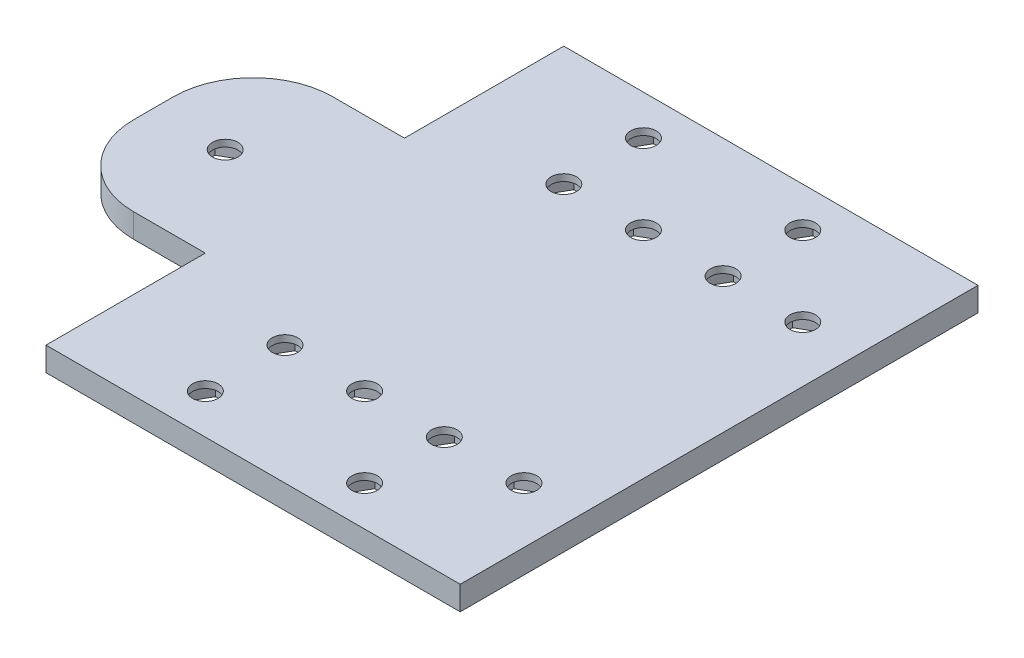
SolidWorks part; units mm, degrees
ref_plane "Front Plane" through (0, 0, 0) normal (0, 0, 1) x (1, 0, 0)
ref_plane "Top Plane" through (0, 0, 0) normal (0, 1, 0) x (1, 0, 0)
ref_plane "Right Plane" through (0, 0, 0) normal (1, 0, 0) x (0, 0, -1)
sketch "Sketch1" plane through (0, 0, 0) normal (0, 1, 0) x (1, 0, 0)
  line L1 (-52, 0) -> (0, 0)
  line L2 (-52, 0) -> (-52, -65)
  line L3 (-52, -65) -> (0, -65)
  line L4 (0, 0) -> (0, -65)
  line L5 (-71, -20) -> (-52, -20)
  line L6 (-71, -20) -> (-71, -45)
  line L7 (-71, -45) -> (-52, -45)
  line L8 (-52, -20) -> (-52, -45)
  dimension "D1" = 52
  dimension "D2" = 65
  dimension "D3" = 20
  dimension "D4" = 20
  dimension "D5" = 19
extrude "Boss-Extrude1" add sketch "Sketch1" along normal blind 3 contours L4 L1 L2 L3 | L6 L7 L2 L5 region at (-26, 0, 32.5) region at (-61.5, 0, 32.5)
sketch "Sketch2" plane through (0, 0, 0) normal (0, -1, 0) x (1, 0, 0)
  line L0 (-46.1813, 60) -> (5.8187, 60) construction
  line L1 (-71, 45) -> (-52, 45) construction
  line L2 (-52, 45) -> (-52, 65) construction
  line L3 (-57.6262, 50) -> (-5.6262, 50) construction
  line L4 (-45.5367, 15) -> (6.4633, 15) construction
  line L5 (-3.975, 48.2535) -> (-3.975, 51.7465)
  line L6 (-3.975, 51.7465) -> (-7, 53.493)
  line L7 (-46.5327, 5) -> (5.4673, 5) construction
  line L8 (-52, 45) -> (-52, 65) construction
  line L9 (0, 0) -> (0, 65) construction
  line L10 (-52, 0) -> (-52, 20) construction
  line L11 (-52, 0) -> (0, 0) construction
  line L12 (-52, 65) -> (0, 65) construction
  line L13 (-27, 80.4391) -> (-27, 0.4391) construction
  line L14 (-33.507, 60) -> (-35.2535, 63.025)
  line L15 (-35.2535, 63.025) -> (-38.7465, 63.025)
  line L16 (-38.7465, 63.025) -> (-40.493, 60)
  line L17 (-40.493, 60) -> (-38.7465, 56.975)
  line L18 (-38.7465, 56.975) -> (-35.2535, 56.975)
  line L19 (-35.2535, 56.975) -> (-33.507, 60)
  line L20 (-18.7465, 56.975) -> (-15.2535, 56.975)
  line L21 (-15.2535, 56.975) -> (-13.507, 60)
  line L22 (-13.507, 60) -> (-15.2535, 63.025)
  line L23 (-15.2535, 63.025) -> (-18.7465, 63.025)
  line L24 (-18.7465, 63.025) -> (-20.493, 60)
  line L25 (-20.493, 60) -> (-18.7465, 56.975)
  line L26 (-15.2535, 46.975) -> (-13.507, 50)
  line L27 (-13.507, 50) -> (-15.2535, 53.025)
  line L28 (-15.2535, 53.025) -> (-18.7465, 53.025)
  line L29 (-18.7465, 53.025) -> (-20.493, 50)
  line L30 (-20.493, 50) -> (-18.7465, 46.975)
  line L31 (-18.7465, 46.975) -> (-15.2535, 46.975)
  line L32 (-35.2535, 46.975) -> (-33.507, 50)
  line L33 (-33.507, 50) -> (-35.2535, 53.025)
  line L34 (-35.2535, 53.025) -> (-38.7465, 53.025)
  line L35 (-38.7465, 53.025) -> (-40.493, 50)
  line L36 (-40.493, 50) -> (-38.7465, 46.975)
  line L37 (-38.7465, 46.975) -> (-35.2535, 46.975)
  line L38 (-35.2535, 11.975) -> (-33.507, 15)
  line L39 (-33.507, 15) -> (-35.2535, 18.025)
  line L40 (-35.2535, 18.025) -> (-38.7465, 18.025)
  line L41 (-38.7465, 18.025) -> (-40.493, 15)
  line L42 (-40.493, 15) -> (-38.7465, 11.975)
  line L43 (-38.7465, 11.975) -> (-35.2535, 11.975)
  line L44 (-15.2535, 11.975) -> (-13.507, 15)
  line L45 (-13.507, 15) -> (-15.2535, 18.025)
  line L46 (-15.2535, 18.025) -> (-18.7465, 18.025)
  line L47 (-18.7465, 18.025) -> (-20.493, 15)
  line L48 (-20.493, 15) -> (-18.7465, 11.975)
  line L49 (-18.7465, 11.975) -> (-15.2535, 11.975)
  line L50 (-13.507, 5) -> (-15.2535, 8.025)
  line L51 (-15.2535, 8.025) -> (-18.7465, 8.025)
  line L52 (-18.7465, 8.025) -> (-20.493, 5)
  line L53 (-20.493, 5) -> (-18.7465, 1.975)
  line L54 (-18.7465, 1.975) -> (-15.2535, 1.975)
  line L55 (-15.2535, 1.975) -> (-13.507, 5)
  line L56 (-38.7465, 8.025) -> (-40.493, 5)
  line L57 (-40.493, 5) -> (-38.7465, 1.975)
  line L58 (-38.7465, 1.975) -> (-35.2535, 1.975)
  line L59 (-35.2535, 1.975) -> (-33.507, 5)
  line L60 (-33.507, 5) -> (-35.2535, 8.025)
  line L61 (-35.2535, 8.025) -> (-38.7465, 8.025)
  line L62 (-62, 62.3352) -> (-62, 22.3352) construction
  line L63 (-23.975, 48.2535) -> (-23.975, 51.7465)
  line L64 (-23.975, 51.7465) -> (-27, 53.493)
  line L65 (-27, 53.493) -> (-30.025, 51.7465)
  line L66 (-30.025, 51.7465) -> (-30.025, 48.2535)
  line L67 (-30.025, 48.2535) -> (-27, 46.507)
  line L68 (-27, 46.507) -> (-23.975, 48.2535)
  line L69 (-23.975, 16.7465) -> (-27, 18.493)
  line L70 (-27, 18.493) -> (-30.025, 16.7465)
  line L71 (-30.025, 16.7465) -> (-30.025, 13.2535)
  line L72 (-30.025, 13.2535) -> (-27, 11.507)
  line L73 (-27, 11.507) -> (-23.975, 13.2535)
  line L74 (-23.975, 13.2535) -> (-23.975, 16.7465)
  line L75 (-7, 53.493) -> (-10.025, 51.7465)
  line L76 (-10.025, 51.7465) -> (-10.025, 48.2535)
  line L77 (-71, 20) -> (-71, 45) construction
  line L84 (-58.975, 34.2465) -> (-62, 35.993)
  line L85 (-62, 35.993) -> (-65.025, 34.2465)
  line L86 (-65.025, 34.2465) -> (-65.025, 30.7535)
  line L87 (-65.025, 30.7535) -> (-62, 29.007)
  line L88 (-62, 29.007) -> (-58.975, 30.7535)
  line L89 (-58.975, 30.7535) -> (-58.975, 34.2465)
  line L90 (-10.025, 48.2535) -> (-7, 46.507)
  line L91 (-7, 46.507) -> (-3.975, 48.2535)
  line L92 (-7, 18.493) -> (-10.025, 16.7465)
  line L93 (-10.025, 16.7465) -> (-10.025, 13.2535)
  line L94 (-10.025, 13.2535) -> (-7, 11.507)
  line L95 (-7, 11.507) -> (-3.975, 13.2535)
  line L96 (-3.975, 13.2535) -> (-3.975, 16.7465)
  line L97 (-3.975, 16.7465) -> (-7, 18.493)
  line L98 (-52, 0) -> (-52, 20) construction
  circle A0 centre (-37, 60) radius 3.025 construction
  circle A1 centre (-17, 60) radius 3.025 construction
  circle A2 centre (-17, 50) radius 3.025 construction
  circle A3 centre (-37, 50) radius 3.025 construction
  circle A4 centre (-37, 15) radius 3.025 construction
  circle A5 centre (-17, 15) radius 3.025 construction
  circle A6 centre (-17, 5) radius 3.025 construction
  circle A7 centre (-37, 5) radius 3.025 construction
  circle A8 centre (-27, 50) radius 3.025 construction
  circle A9 centre (-27, 15) radius 3.025 construction
  circle A10 centre (-7, 50) radius 3.025 construction
  circle A11 centre (-62, 32.5) radius 3.025 construction
  circle A12 centre (-7, 15) radius 3.025 construction
  point P3 (-37, 60)
  point P4 (-17, 50)
  point P5 (-17, 60)
  point P7 (-37, 50)
  point P9 (-37, 5)
  point P13 (-17, 15)
  point P16 (-17, 5)
  point P24 (-37, 15)
  point P91 (-27, 50)
  point P93 (-27, 15)
  point P112 (-62, 32.5)
  point P118 (-7, 50)
  point P120 (-7, 15)
  point P148 (-47, 15)
  point P149 (-6.6463, 15)
  point P150 (-7.2745, 50)
  dimension "D13" = 6.05
  dimension "D14" = 6.05
  dimension "D15" = 6.05
  dimension "D16" = 6.05
  dimension "D17" = 6.05
  dimension "D18" = 6.05
  dimension "D19" = 6.05
  dimension "D20" = 6.05
  dimension "D21" = 6.05
  dimension "D22" = 6.05
  dimension "D26" = 6.05
  dimension "D27" = 12.5
  dimension "D28" = 6.05
  dimension "D29" = 6.05
  dimension "D1" = 15
  dimension "D2" = 17
  dimension "D3" = 17
  dimension "D4" = 15
  dimension "D5" = 15
  dimension "D6" = 17
  dimension "D7" = 15
  dimension "D8" = 17
  dimension "D9" = 5
  dimension "D10" = 15
  dimension "D11" = 5
  dimension "D12" = 15
  dimension "D23" = 15
  dimension "D24" = 15
  dimension "D25" = 27
  dimension "D30" = 9
  dimension "D31" = 10
  dimension "D32" = 10
extrude "Cut-Extrude1" cut sketch "Sketch2" against normal blind 2.15 contours L88 L89 L84 L85 L86 L87 | L36 L37 L32 L33 L34 L35 | L18 L19 L14 L15 L16 L17 | L24 L25 L20 L21 L22 L23 | L30 L31 L26 L27 L28 L29 | L67 L68 L63 L64 L65 L66 | L73 L74 L69 L70 L71 L72 | L48 L49 L44 L45 L46 L47 | L54 L55 L50 L51 L52 L53 | L60 L61 L56 L57 L58 L59 | L42 L43 L38 L39 L40 L41 | L90 L91 L5 L6 L75 L76 | L96 L97 L92 L93 L94 L95 region at (-7, 0, 50) region at (-37, 0, 60) region at (-17, 0, 60) region at (-17, 0, 50) region at (-37, 0, 50) region at (-37, 0, 15) region at (-17, 0, 15) region at (-17, 0, 5) region at (-37, 0, 5) region at (-27, 0, 50) region at (-27, 0, 15) region at (-62, 0, 32.5) region at (-7, 0, 15)
hole_wizard "Hole1" positions "3DSketch1" profile "Sketch3" legacy end condition through all
sketch3d "3DSketch1"
  point P0 (-37, 0, 5)
  point P3 (-37, 0, 15)
  point P6 (-17, 0, 15)
  point P9 (-17, 0, 5)
  point P12 (-27, 0, 15)
  point P15 (-27, 0, 50)
  point P18 (-17, 0, 50)
  point P21 (-17, 0, 60)
  point P24 (-37, 0, 60)
  point P27 (-37, 0, 50)
  point P30 (-62, 0, 32.5)
  point P33 (-7, 0, 15)
  point P36 (-7, 0, 50)
sketch "Sketch3" plane through (-37, 0, 5) normal (1, 0, 0) x (0, 0, -1)
  line L0 (0, 0) -> (0, 3)
  line L1 (0, 3) -> (1.6, 3)
  line L2 (1.6, 3) -> (1.6, 0)
  line L3 (1.6, 0) -> (0, 0)
  line L4 (0, 110) -> (0, -10) construction
  dimension "Diameter" = 3.2
  dimension "Depth" = 3
fillet "Fillet1" radius 10 2 edges at (-71, 1.5, 20) (-71, 1.5, 45)
